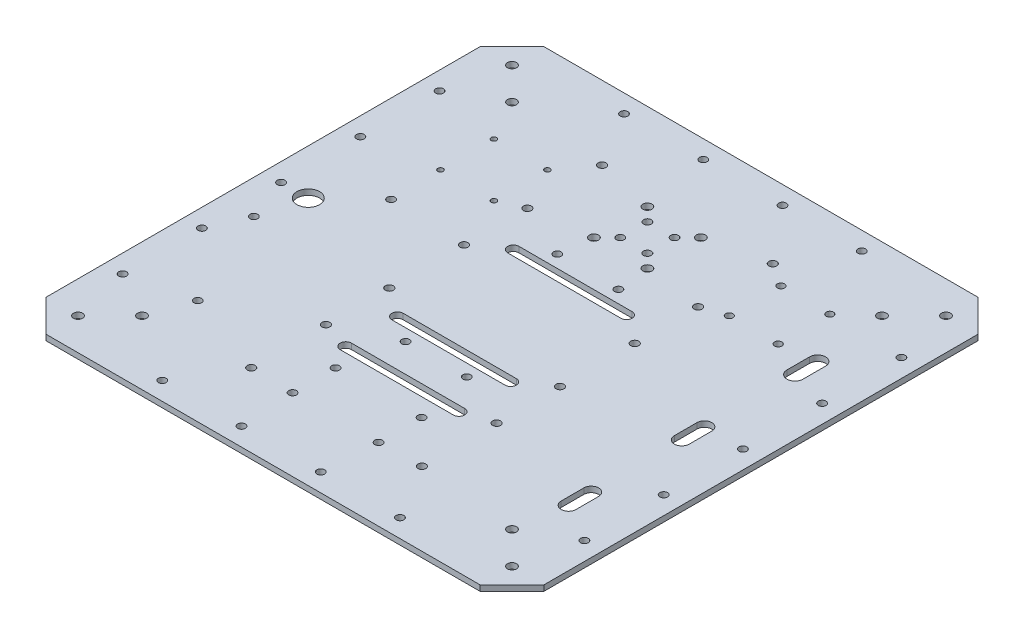
SolidWorks part; units mm, degrees
ref_plane "Front Plane" through (0, 0, 0) normal (0, 0, 1) x (1, 0, 0)
ref_plane "Top Plane" through (0, 0, 0) normal (0, 1, 0) x (1, 0, 0)
ref_plane "Right Plane" through (0, 0, 0) normal (1, 0, 0) x (0, 0, -1)
sketch "Sketch1" plane through (0, 0, 0) normal (0, 1, 0) x (1, 0, 0)
  line L0 (-160.4847, 61.5307) -> (-142.5242, 79.4912)
  line L1 (-160.4847, 79.4912) -> (118.9153, 79.4912)
  line L2 (-160.4847, 79.4912) -> (-160.4847, -199.9088)
  line L3 (-160.4847, -199.9088) -> (118.9153, -199.9088)
  line L4 (118.9153, 79.4912) -> (118.9153, -199.9088)
  line L5 (-20.7847, 79.4912) -> (-20.7847, -199.9088) construction
  line L6 (-160.4847, -60.2088) -> (118.9153, -60.2088) construction
  line L7 (118.9153, 61.5307) -> (100.9548, 79.4912)
  line L8 (118.9153, -181.9483) -> (100.9548, -199.9088)
  line L9 (-160.4847, -181.9483) -> (-142.5242, -199.9088)
  line L10 (-268.2478, 187.2542) -> (226.6783, -307.6719) construction
  line L11 (226.6783, -307.6719) -> (226.6783, 187.2542) construction
  line L12 (226.6783, 187.2542) -> (-268.2478, -307.6719) construction
  line L13 (-268.2478, -307.6719) -> (-268.2478, 187.2542) construction
  line L14 (-268.2478, 187.2542) -> (226.6783, 187.2542) construction
  line L15 (-268.2478, -307.6719) -> (226.6783, -307.6719) construction
  line L16 (-151.5045, 70.5109) -> (-268.2478, 187.2542) construction
  point P8 (-20.7847, 79.4912)
  point P11 (-160.4847, -60.2088)
  point P19 (118.9153, -60.2088)
  point P20 (-20.7847, -199.9088)
  point P22 (-151.5045, 70.5109)
  point P25 (-20.7847, -60.2088)
  point P26 (-20.7847, -60.2088)
  dimension "D1" = 279.4
  dimension "D2" = 279.4
  dimension "D3" = 165.1
  dimension "D4" = 25.4
extrude "Boss-Extrude1" add sketch "Sketch1" along normal blind 3.175 contours L2 L9 L3 L8 L4 L7 L1 L0 region at (-20.7847, 0, 60.2088)
sketch "Sketch2" plane through (0, 3.175, 0) normal (0, 1, 0) x (1, 0, 0)
  line L0 (-20.7847, 79.4912) -> (-20.7847, -287.8465) construction
  line L1 (-142.5242, 79.4912) -> (100.9548, 79.4912) construction
  line L2 (118.9153, -60.2088) -> (-158.2106, -60.2088) construction
  line L3 (118.9153, 61.5307) -> (118.9153, -181.9483) construction
  circle A0 centre (-38.0567, -17.5368) radius 2.159
  circle A1 centre (-3.7667, -17.5368) radius 2.159
  circle A2 centre (-38.0567, -102.6268) radius 2.159
  circle A3 centre (-3.7667, -102.6268) radius 2.159
  dimension "D5" = 4.318
  dimension "D6" = 4.318
  dimension "D7" = 4.318
  dimension "D8" = 4.318
  dimension "D1" = 17.272
  dimension "D2" = 34.29
  dimension "D3" = 85.09
  dimension "D4" = 42.672
extrude "Cut-Extrude1" cut sketch "Sketch2" against normal through all
sketch "Sketch4" plane through (0, 3.175, 0) normal (0, 1, 0) x (1, 0, 0)
  line L0 (-52.5347, -27.7088) -> (10.9653, -27.7088) construction
  line L1 (-52.5347, -24.5338) -> (10.9653, -24.5338)
  line L2 (-52.5347, -30.8838) -> (10.9653, -30.8838)
  line L3 (-52.5347, -92.7088) -> (10.9653, -92.7088) construction
  line L4 (-52.5347, -89.5338) -> (10.9653, -89.5338)
  line L5 (-52.5347, -95.8838) -> (10.9653, -95.8838)
  line L6 (118.9153, 61.5307) -> (118.9153, -181.9483) construction
  line L7 (-20.7847, -92.7088) -> (-20.7847, -198.1921) construction
  line L8 (-160.4847, -60.2088) -> (118.9153, -60.2088) construction
  line L9 (-160.4847, 61.5307) -> (-160.4847, -181.9483) construction
  line L14 (-52.5347, -121.708) -> (10.9653, -121.708) construction
  line L15 (-52.5347, -118.533) -> (10.9653, -118.533)
  line L16 (-52.5347, -124.883) -> (10.9653, -124.883)
  line L17 (-20.7847, -27.7088) -> (-20.7847, -92.7088) construction
  arc A0 (-52.5347, -24.5338) -> (-52.5347, -30.8838) centre (-52.5347, -27.7088) ccw
  arc A1 (10.9653, -30.8838) -> (10.9653, -24.5338) centre (10.9653, -27.7088) ccw
  arc A2 (-52.5347, -89.5338) -> (-52.5347, -95.8838) centre (-52.5347, -92.7088) ccw
  arc A3 (10.9653, -95.8838) -> (10.9653, -89.5338) centre (10.9653, -92.7088) ccw
  arc A7 (-52.5347, -118.533) -> (-52.5347, -124.883) centre (-52.5347, -121.708) ccw
  arc A8 (10.9653, -124.883) -> (10.9653, -118.533) centre (10.9653, -121.708) ccw
  point P2 (-20.7847, -27.7088)
  point P7 (-20.7847, -92.7088)
  point P18 (-20.7847, -60.2088)
  point P19 (-20.7847, -60.2088)
  point P33 (-20.7847, -121.708)
  dimension "D1" = 63.5
  dimension "D2" = 63.5
  dimension "D3" = 6.35
  dimension "D4" = 6.35
  dimension "D5" = 65
  dimension "D6" = 28.9992
  dimension "D8" = 63.5
  dimension "D9" = 6.35
extrude "Cut-Extrude2" cut sketch "Sketch4" against normal through all
sketch "Sketch7" plane through (0, 3.175, 0) normal (0, 1, 0) x (1, 0, 0)
  line L0 (-96.7307, 89.5196) -> (-96.7307, -24.0818) construction
  line L1 (-160.4847, -60.2088) -> (118.9153, -60.2088) construction
  line L2 (-160.4847, 61.5307) -> (-160.4847, -181.9483) construction
  line L3 (118.9153, 61.5307) -> (118.9153, -181.9483) construction
  line L4 (-20.7847, 79.4912) -> (-20.7847, -252.674) construction
  line L5 (-142.5242, 79.4912) -> (100.9548, 79.4912) construction
  circle A0 centre (-81.7447, 20.5632) radius 1.524
  circle A1 centre (-81.7447, -9.4088) radius 1.524
  circle A2 centre (-111.7167, -9.4088) radius 1.524
  circle A3 centre (-111.7167, 20.5632) radius 1.524
  dimension "D1" = 3.048
  dimension "D2" = 14.986
  dimension "D4" = 29.972
  dimension "D3" = 3.048
  dimension "D5" = 50.8
  dimension "D6" = 60.96
  dimension "D7" = 14.986
extrude "Cut-Extrude3" cut sketch "Sketch7" against normal through all
sketch "Sketch8" plane through (0, 3.175, 0) normal (0, 1, 0) x (1, 0, 0)
  line L0 (-142.5242, -199.9088) -> (100.9548, -199.9088) construction
  line L1 (118.9153, 61.5307) -> (118.9153, -181.9483) construction
  circle A0 centre (8.4253, -175.0168) radius 1.524
  circle A1 centre (8.4253, -144.5368) radius 1.524
  circle A2 centre (32.3013, -175.0168) radius 1.524
  circle A3 centre (32.3013, -144.5368) radius 1.524
  dimension "D1" = 3.048
  dimension "D2" = 30.48
  dimension "D3" = 23.876
  dimension "D4" = 24.892
  dimension "D5" = 86.614
extrude "Cut-Extrude4" [suppressed] cut sketch "Sketch8" against normal through all and the other way through all
sketch "Sketch10" plane through (0, 0, 0) normal (0, -1, 0) x (1, 0, 0)
  line L0 (-142.5242, 199.9088) -> (100.9548, 199.9088) construction
  line L1 (-20.7847, 199.9088) -> (-20.7847, 128.7119) construction
  line L2 (-52.5347, 124.883) -> (10.9653, 124.883) construction
  circle A0 centre (-44.9147, 159.173) radius 2.159
  circle A1 centre (3.3453, 159.173) radius 2.159
  circle A2 centre (-44.9147, 135.043) radius 2.159
  circle A3 centre (3.3453, 135.043) radius 2.159
  dimension "D1" = 4.318
  dimension "D2" = 48.26
  dimension "D4" = 10.16
  dimension "D6" = 4.318
  dimension "D7" = 4.318
  dimension "D8" = 4.318
  dimension "D3" = 24.13
  dimension "D5" = 24.13
extrude "Cut-Extrude6" cut sketch "Sketch10" against normal through all
sketch "Sketch9" plane through (0, 0, 0) normal (0, -1, 0) x (-1, 0, 0)
  line L1 (160.4847, -60.2088) -> (-327.4314, -60.2088) construction
  line L2 (-53.8913, -43.6513) -> (-53.8913, -126.5783) construction
  line L3 (20.7847, 79.4912) -> (20.7847, -331.7119) construction
  line L4 (142.5242, 79.4912) -> (-100.9548, 79.4912) construction
  line L7 (160.4847, 61.5307) -> (160.4847, -181.9483) construction
  circle A0 centre (-40.1753, 0.7512) radius 2.032
  circle A1 centre (-67.6073, 0.7512) radius 2.032
  circle A2 centre (-40.1753, 29.7072) radius 2.032
  circle A3 centre (-67.6073, 29.7072) radius 2.032
  dimension "D1" = 4.064
  dimension "D9" = 4.064
  dimension "D2" = 60.96
  dimension "D3" = 28.956
  dimension "D4" = 60.96
  dimension "D8" = 13.716
extrude "Cut-Extrude5" cut sketch "Sketch9" against normal through all
sketch "Sketch13" plane through (0, 0, 0) normal (0, -1, 0) x (1, 0, 0)
  line L0 (-20.7847, -79.4912) -> (-20.7847, 261.4711) construction
  line L1 (-142.5242, -79.4912) -> (100.9548, -79.4912) construction
  line L2 (-160.4847, 60.2088) -> (239.2508, 60.2088) construction
  line L3 (-160.4847, -61.5307) -> (-160.4847, 181.9483) construction
  line L4 (-35.7847, -30.7512) -> (-35.7847, -0.7512) construction
  line L5 (-35.7847, -15.7512) -> (8.2736, -15.7512) construction
  circle A0 centre (-35.7847, -0.7512) radius 2.54
  circle A1 centre (-35.7847, -30.7512) radius 2.54
  circle A2 centre (-5.7847, -30.7512) radius 2.54
  circle A3 centre (-5.7847, -0.7512) radius 2.54
  circle A4 centre (-28.4047, -23.3712) radius 2.159
  circle A5 centre (-28.4047, -8.1312) radius 2.159
  circle A6 centre (-13.1647, -8.1312) radius 2.159
  circle A7 centre (-13.1647, -23.3712) radius 2.159
  dimension "D1" = 5.08
  dimension "D2" = 5.08
  dimension "D6" = 4.318
  dimension "D7" = 15.24
  dimension "D3" = 30
  dimension "D4" = 15
  dimension "D5" = 60.96
  dimension "D8" = 15.24
extrude "Cut-Extrude8" cut sketch "Sketch13" against normal through all
sketch "Sketch14" plane through (0, 0, 0) normal (0, -1, 0) x (1, 0, 0)
  line L0 (-20.7847, 199.9088) -> (-20.7847, -154.5354) construction
  line L1 (-142.5242, 199.9088) -> (100.9548, 199.9088) construction
  line L2 (-160.4847, 60.2088) -> (331.9066, 60.2088) construction
  line L3 (-160.4847, -61.5307) -> (-160.4847, 181.9483) construction
  line L4 (-160.4847, 181.9483) -> (-142.5242, 199.9088) construction
  line L5 (-268.2478, -187.2542) -> (226.6783, 307.6719) construction
  line L6 (-268.2478, -187.2542) -> (226.6783, -187.2542) construction
  line L7 (-268.2478, -187.2542) -> (-268.2478, 307.6719) construction
  line L8 (-160.4847, 181.9483) -> (-142.5242, 199.9088) construction
  line L9 (-151.5045, 190.9286) -> (-83.1439, 122.568) construction
  line L10 (-268.2478, 307.6719) -> (226.6783, 307.6719) construction
  line L11 (226.6783, -187.2542) -> (226.6783, 307.6719) construction
  line L12 (226.6783, -187.2542) -> (-268.2478, 307.6719) construction
  line L14 (-160.4847, -61.5307) -> (-142.5242, -79.4912) construction
  line L21 (-268.2478, -187.2542) -> (-151.5045, -70.5109) construction
  line L22 (109.935, -70.5109) -> (226.6783, -187.2542) construction
  line L23 (118.9153, -61.5307) -> (100.9548, -79.4912) construction
  line L24 (109.935, 190.9286) -> (226.6783, 307.6719) construction
  line L25 (118.9153, 181.9483) -> (100.9548, 199.9088) construction
  line L26 (-268.2478, 307.6719) -> (-151.5045, 190.9286) construction
  circle A1 centre (-142.5242, 181.9483) radius 2.54
  circle A3 centre (-124.5637, 163.9878) radius 2.54
  circle A4 centre (82.9942, 163.9878) radius 2.54
  circle A7 centre (100.9548, 181.9483) radius 2.54
  circle A8 centre (-142.5242, -61.5307) radius 2.54
  circle A11 centre (-124.5637, -43.5701) radius 2.54
  circle A14 centre (100.9548, -61.5307) radius 2.54
  circle A15 centre (82.9942, -43.5701) radius 2.54
  point P8 (-20.7847, 60.2088)
  point P30 (226.6783, 60.2088)
  point P33 (-151.5045, -70.5109)
  point P36 (-20.7847, -187.2542)
  dimension "D3" = 5.08
  dimension "D6" = 5.08
  dimension "D1" = 12.7
  dimension "D2" = 165.1
  dimension "D9" = 25.4
extrude "Cut-Extrude9" cut sketch "Sketch14" against normal through all
sketch "Sketch15" plane through (0, 0, 0) normal (0, -1, 0) x (1, 0, 0)
  line L0 (-20.7847, 199.9088) -> (-20.7847, 125.875) construction
  line L1 (-142.5242, 199.9088) -> (100.9548, 199.9088) construction
  line L2 (-160.4847, 60.2088) -> (75.4631, 60.2088) construction
  line L3 (-160.4847, -61.5307) -> (-160.4847, 181.9483) construction
  circle A0 centre (-43.0097, 189.7488) radius 2.159
  circle A1 centre (-87.4597, 189.7488) radius 2.159
  circle A2 centre (-150.3247, 60.2088) radius 2.159
  circle A3 centre (-150.3247, 104.6588) radius 2.159
  circle A4 centre (-150.3247, 149.1088) radius 2.159
  circle A5 centre (108.7553, 149.1088) radius 2.159
  circle A6 centre (108.7553, 104.6588) radius 2.159
  circle A7 centre (108.7553, 60.2088) radius 2.159
  circle A8 centre (45.8903, 189.7488) radius 2.159
  circle A9 centre (1.4403, 189.7488) radius 2.159
  circle A10 centre (1.4403, -69.3312) radius 2.159
  circle A11 centre (45.8903, -69.3312) radius 2.159
  circle A12 centre (108.7553, 15.7588) radius 2.159
  circle A13 centre (108.7553, -28.6912) radius 2.159
  circle A14 centre (-150.3247, -28.6912) radius 2.159
  circle A15 centre (-150.3247, 15.7588) radius 2.159
  circle A16 centre (-87.4597, -69.3312) radius 2.159
  circle A17 centre (-43.0097, -69.3312) radius 2.159
  dimension "D3" = 4.318
  dimension "D4" = 4.318
  dimension "D8" = 4.318
  dimension "D9" = 4.318
  dimension "D10" = 4.318
  dimension "D1" = 22.225
  dimension "D2" = 44.45
  dimension "D5" = 10.16
  dimension "D6" = 44.45
  dimension "D7" = 44.45
  dimension "D11" = 10.16
extrude "Cut-Extrude10" cut sketch "Sketch15" against normal through all
sketch "Sketch16" plane through (0, 0, 0) normal (0, -1, 0) x (-1, 0, 0)
  line L0 (20.7847, 79.4912) -> (20.7847, -323.0503) construction
  line L1 (-49.3193, -131.0748) -> (-89.9593, -131.0748)
  line L2 (-49.3193, -131.0748) -> (-49.3193, -47.5088)
  line L3 (-49.3193, -47.5088) -> (-89.9593, -47.5088)
  line L4 (-89.9593, -131.0748) -> (-89.9593, -47.5088)
  line L5 (131.5287, -131.0748) -> (131.5287, -47.5088)
  line L6 (142.5242, 79.4912) -> (-100.9548, 79.4912) construction
  line L7 (160.4847, -60.2088) -> (-312.3855, -60.2088) construction
  line L8 (160.4847, 61.5307) -> (160.4847, -181.9483) construction
  line L9 (90.8887, -47.5088) -> (131.5287, -47.5088)
  line L10 (90.8887, -131.0748) -> (90.8887, -47.5088)
  line L11 (90.8887, -131.0748) -> (131.5287, -131.0748)
  circle A0 centre (-74.7193, -140.9808) radius 2.159
  circle A1 centre (-69.6393, -37.6028) radius 2.159
  circle A2 centre (-99.8653, -84.4248) radius 2.159
  circle A3 centre (141.4347, -84.4248) radius 2.159
  circle A4 centre (111.2087, -37.6028) radius 2.159
  circle A5 centre (116.2887, -140.9808) radius 2.159
  dimension "D3" = 9.906
  dimension "D4" = 9.906
  dimension "D5" = 9.906
  dimension "D6" = 15.24
  dimension "D7" = 20.32
  dimension "D8" = 46.65
  dimension "D9" = 4.318
  dimension "D10" = 4.318
  dimension "D11" = 4.318
  dimension "D1" = 83.566
  dimension "D2" = 40.64
  dimension "D12" = 120.65
  dimension "D13" = 12.7
extrude "Cut-Extrude11" cut sketch "Sketch16" against normal through all contours A5 | A3 | A4
sketch "Sketch17" plane through (0, 3.175, 0) normal (0, 1, 0) x (1, 0, 0)
  line L2 (-20.7847, 79.4912) -> (-20.7847, -395.818) construction
  line L3 (-142.5242, 79.4912) -> (100.9548, 79.4912) construction
  line L4 (118.9153, -60.2088) -> (-127.1454, -60.2088) construction
  line L5 (118.9153, 61.5307) -> (118.9153, -181.9483) construction
  circle A12 centre (27.0943, -158.6338) radius 2.2225
  circle A13 centre (-68.6637, -158.6338) radius 2.2225
  circle A14 centre (27.0943, -116.7238) radius 2.2225
  circle A15 centre (-68.6637, -116.7238) radius 2.2225
  circle A16 centre (27.0943, -81.1638) radius 2.2225
  circle A17 centre (-68.6637, -81.1638) radius 2.2225
  circle A18 centre (27.0943, -39.2538) radius 2.2225
  circle A19 centre (-68.6637, -39.2538) radius 2.2225
  circle A20 centre (27.0943, -3.6938) radius 2.2225
  circle A21 centre (-68.6637, -3.6938) radius 2.2225
  circle A22 centre (27.0943, 38.2162) radius 2.2225
  circle A23 centre (-68.6637, 38.2162) radius 2.2225
  circle A24 centre (-68.6637, 38.2162) radius 2.2225
  circle A25 centre (27.0943, 38.2162) radius 2.2225
  circle A26 centre (-68.6637, -3.6938) radius 2.2225
  circle A27 centre (27.0943, -3.6938) radius 2.2225
  circle A28 centre (-68.6637, -39.2538) radius 2.2225
  circle A29 centre (27.0943, -39.2538) radius 2.2225
  circle A30 centre (-68.6637, -81.1638) radius 2.2225
  circle A31 centre (27.0943, -81.1638) radius 2.2225
  circle A32 centre (-68.6637, -116.7238) radius 2.2225
  circle A33 centre (27.0943, -116.7238) radius 2.2225
  circle A34 centre (-68.6637, -158.6338) radius 2.2225
  dimension "D1" = 4.445
  dimension "D2" = 4.445
  dimension "D3" = 4.445
  dimension "D4" = 4.445
  dimension "D5" = 4.445
  dimension "D6" = 4.445
  dimension "D7" = 4.445
  dimension "D8" = 4.445
  dimension "D9" = 4.445
  dimension "D10" = 4.445
  dimension "D11" = 4.445
  dimension "D12" = 4.445
  dimension "D25" = 56.515
  dimension "D24" = 56.515
  dimension "D13" = 95.758
  dimension "D14" = 41.91
  dimension "D15" = 95.758
  dimension "D16" = 41.91
  dimension "D17" = 95.758
  dimension "D18" = 41.91
  dimension "D19" = 47.879
  dimension "D20" = 47.879
  dimension "D21" = 47.879
  dimension "D22" = 20.955
extrude "Cut-Extrude13" cut sketch "Sketch17" against normal through all contours A23 | A22 | A20 | A21 | A18 | A19 | A17 | A16 | A12 | A14 | A15 | A13
sketch "Sketch18" [suppressed] plane through (0, 3.175, 0) normal (0, 1, 0) x (1, 0, 0)
  line L1 (-142.5242, -199.9088) -> (-160.4847, -181.9483)
  line L2 (-142.5242, -199.9088) -> (-106.6032, -163.9878)
  line L3 (-106.6032, -163.9878) -> (-124.5637, -146.0273)
  line L4 (-160.4847, -181.9483) -> (-124.5637, -146.0273)
  line L5 (-20.7847, 79.4912) -> (-20.7847, -264.9481) construction
  line L6 (-142.5242, 79.4912) -> (100.9548, 79.4912) construction
  line L7 (118.9153, -60.2088) -> (-155.4453, -60.2088) construction
  line L8 (118.9153, 61.5307) -> (118.9153, -181.9483) construction
  line L9 (-160.4847, 61.5307) -> (-124.5637, 25.6096)
  line L10 (-106.6032, 43.5701) -> (-124.5637, 25.6096)
  line L11 (-142.5242, 79.4912) -> (-106.6032, 43.5701)
  line L12 (-142.5242, 79.4912) -> (-160.4847, 61.5307)
  line L13 (100.9548, 79.4912) -> (118.9153, 61.5307)
  line L14 (100.9548, 79.4912) -> (65.0337, 43.5701)
  line L15 (65.0337, 43.5701) -> (82.9942, 25.6096)
  line L16 (118.9153, 61.5307) -> (82.9942, 25.6096)
  line L17 (118.9153, -181.9483) -> (82.9942, -146.0273)
  line L18 (65.0337, -163.9878) -> (82.9942, -146.0273)
  line L19 (100.9548, -199.9088) -> (65.0337, -163.9878)
  line L20 (100.9548, -199.9088) -> (118.9153, -181.9483)
  line L21 (-142.5242, -181.9483) -> (-124.5637, -163.9878) construction
  line L22 (-160.4847, -181.9483) -> (-142.5242, -199.9088) construction
  line L23 (-160.4847, -181.9483) -> (-142.5242, -199.9088) construction
  circle A2 centre (-124.5637, -163.9878) radius 2.54 construction
  circle A3 centre (-142.5242, -181.9483) radius 2.54 construction
  circle A4 centre (-124.5637, -163.9878) radius 2.54 construction
  circle A5 centre (-142.5242, -181.9483) radius 2.54 construction
  point P12 (-151.5045, -190.9286)
  point P33 (-151.5045, -190.9286)
  dimension "D1" = 50.8
  dimension "D2" = 25.4
sketch "Sketch19" plane through (0, 3.175, 0) normal (0, 1, 0) x (1, 0, 0)
  line L0 (87.1653, -136.4088) -> (87.1653, -123.7088) construction
  line L1 (83.0169, -136.4088) -> (83.0169, -123.7088)
  line L2 (91.3137, -136.4088) -> (91.3137, -123.7088)
  line L3 (87.1653, -72.9088) -> (87.1653, -60.2088) construction
  line L4 (83.0169, -72.9088) -> (83.0169, -60.2088)
  line L5 (91.3137, -72.9088) -> (91.3137, -60.2088)
  line L6 (87.1653, -9.4088) -> (87.1653, 3.2912) construction
  line L7 (82.6711, -9.4088) -> (82.6711, 3.2912)
  line L8 (91.6594, -9.4088) -> (91.6594, 3.2912)
  line L9 (118.9153, 61.5307) -> (118.9153, -181.9483) construction
  line L10 (-142.5242, -199.9088) -> (100.9548, -199.9088) construction
  arc A0 (83.0169, -136.4088) -> (91.3137, -136.4088) centre (87.1653, -136.4088) ccw
  arc A1 (91.3137, -123.7088) -> (83.0169, -123.7088) centre (87.1653, -123.7088) ccw
  arc A2 (83.0169, -72.9088) -> (91.3137, -72.9088) centre (87.1653, -72.9088) ccw
  arc A3 (91.3137, -60.2088) -> (83.0169, -60.2088) centre (87.1653, -60.2088) ccw
  arc A4 (82.6711, -9.4088) -> (91.6594, -9.4088) centre (87.1653, -9.4088) ccw
  arc A5 (91.6594, 3.2912) -> (82.6711, 3.2912) centre (87.1653, 3.2912) ccw
  point P2 (87.1653, -130.0588)
  point P7 (87.1653, -66.5588)
  point P14 (87.1653, -3.0588)
  dimension "D1" = 12.7
  dimension "D2" = 12.7
  dimension "D3" = 12.7
  dimension "D4" = 50.8
  dimension "D5" = 50.8
  dimension "D6" = 31.75
  dimension "D7" = 63.5
extrude "Cut-Extrude14" cut sketch "Sketch19" against normal through all
sketch "Sketch20" plane through (0, 3.175, 0) normal (0, 1, 0) x (1, 0, 0)
  line L0 (-160.4847, -60.2088) -> (142.2929, -60.2088) construction
  line L1 (-160.4847, 61.5307) -> (-160.4847, -181.9483) construction
  line L2 (-20.7847, 79.4912) -> (-20.7847, -217.6785) construction
  line L3 (-142.5242, 79.4912) -> (100.9548, 79.4912) construction
  circle A0 centre (-135.0847, -60.2088) radius 6.35
  point P10 (0, 0)
  point P11 (0, 0)
  dimension "D1" = 12.7
  dimension "D2" = 25.4
extrude "Cut-Extrude15" cut sketch "Sketch20" against normal through all
